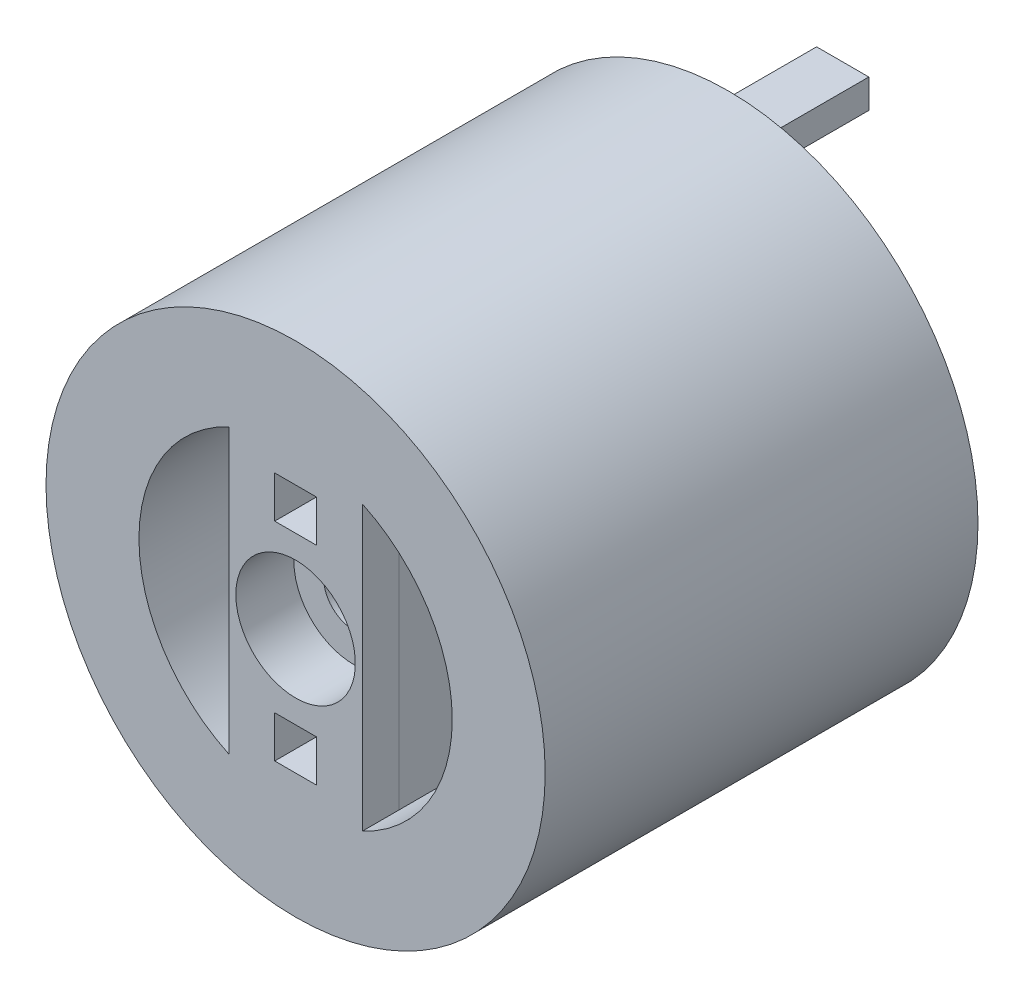
SolidWorks part; units mm, degrees
ref_plane "Front Plane" through (0, 0, 0) normal (0, 0, 1) x (1, 0, 0)
ref_plane "Top Plane" through (0, 0, 0) normal (0, 1, 0) x (1, 0, 0)
ref_plane "Right Plane" through (0, 0, 0) normal (1, 0, 0) x (0, 0, -1)
sketch "Sketch1" plane through (0, 0, 0) normal (0, 0, 1) x (1, 0, 0)
  line L0 (14.5003, 0) -> (13.5003, 0)
  line L1 (0, 16.2503) -> (0, 13.5003)
  line L3 (0, -13.5003) -> (0, -21.51)
  line L4 (13.5003, 0) -> (-13.5003, 0)
  line L8 (19.5347, 4.9654) -> (14.5348, 4.9999)
  line L9 (19.5347, 4.9654) -> (19.4657, -5.0344)
  line L10 (19.4657, -5.0344) -> (14.4659, -4.9999)
  line L11 (14.5348, 4.9999) -> (14.4659, -4.9999)
  line L24 (-2.25, 18.7503) -> (-2.25, 16.2503)
  line L25 (-2.25, 18.7503) -> (2.25, 18.7503)
  line L26 (2.25, 18.7503) -> (2.25, 16.2503)
  line L27 (-2.25, 16.2503) -> (2.25, 16.2503)
  circle A0 centre (0, 0) radius 13.5003
  circle A1 centre (0, 0) radius 21.51
  point P0 (0, 16.2503)
  point P1 (14.5003, 0)
  dimension "D3" = 4.5
  dimension "D5" = 4.9
  dimension "D1" = 1
  dimension "D2" = 2.75
  dimension "D4" = 2.5
  dimension "D6" = 5
  dimension "D7" = 10
extrude "Boss-Extrude1" add sketch "Sketch1" along normal blind 37.3 contours A1 L11 L8 L9 L10 L27 L24 L25 L26 A0 | L24 L27 L26 L25 | L8 L11 L10 L9 | L3 A1 L9 L10 L11 L0 A0 region at (-14.7797, 14.7797, 0) region at (0, 17.5003, 0) region at (17.0003, -0.0172, 0)
extrude "Boss-Extrude2" add sketch "Sketch1<4>" against normal blind 9.85 contours L25 L26 L27 L24
sketch "Sketch1<4>" plane through (0, 0, 0) normal (0, 0, 1) x (1, 0, 0) same geometry as "Sketch1"
sketch "Sketch3" plane through (0, 0, 0) normal (0, 1, 0) x (1, 0, 0)
  line L0 (0, -26.5014) -> (0, 0)
pattern_circular "CirPattern2" count 2 over 360 about axis through (0, 0, 26.5014) along (0, 0, -1) of "Boss-Extrude2" reverse direction yes
sketch "Sketch4" plane through (0, 0, 37.3) normal (0, 0, 1) x (1, 0, 0)
  line L1 (5.75, -19.1684) -> (-5.75, -19.1684)
  line L2 (5.75, -19.1684) -> (5.75, 19.1684)
  line L3 (5.75, 19.1684) -> (-5.75, 19.1684)
  line L4 (-5.75, -19.1684) -> (-5.75, 19.1684)
  line L5 (5.75, -19.1684) -> (-5.75, 19.1684) construction
  line L6 (5.75, 19.1684) -> (-5.75, -19.1684) construction
  line L7 (-5.75, 5.75) -> (5.75, 5.75)
  line L8 (-5.75, 5.75) -> (-5.75, -5.75)
  line L9 (-5.75, -5.75) -> (5.75, -5.75)
  line L10 (5.75, 5.75) -> (5.75, -5.75)
  line L11 (-5.75, 5.75) -> (5.75, -5.75) construction
  line L12 (-5.75, -5.75) -> (5.75, 5.75) construction
  point P0 (0, 0)
  point P5 (0, 0)
  dimension "D1" = 11.5
extrude "Boss-Extrude3" add sketch "Sketch4" against normal blind 3.175 contours L4 L3 L2 L1
sketch "Sketch8" plane through (0, 0, 34.125) normal (0, 0, 1) x (1, 0, 0)
  line L0 (0, -2.5875) -> (0, -16.4823)
  line L5 (5.7476, 16.4823) -> (-5.7476, 16.4823)
  line L6 (5.7476, 16.4823) -> (5.7476, -16.4823)
  line L11 (5.7476, -16.4823) -> (-5.7476, -16.4823)
  line L12 (-5.7476, 16.4823) -> (-5.7476, -16.4823)
  line L13 (5.7476, 16.4823) -> (-5.7476, -16.4823) construction
  line L14 (5.7476, -16.4823) -> (-5.7476, 16.4823) construction
  circle A1 centre (0, 0) radius 2.5875
  point P0 (0, 0)
  dimension "D2" = 11.4952
extrude "Boss-Extrude4" add sketch "Sketch8" against normal blind 5 contours L5 L12 L11 L6 | A1
extrude "Cut-Extrude1" cut sketch "Sketch1<3>" along normal blind 23 contours L8 L11 L10 L9 region at (17.0003, -0.0172, 0)
sketch "Sketch1<3>" plane through (0, 0, 0) normal (0, 0, 1) x (1, 0, 0) same geometry as "Sketch1"
pattern_circular "CirPattern1" count 2 every 53 about axis through (0, 0, 26.5014) along (0, 0, -1) of "Cut-Extrude1" reverse direction yes other way count 2
mirror "Mirror2" about plane through (0, 0, 0) normal (1, 0, 0) of "CirPattern1"
sketch "Sketch7" plane through (0, 0, 37.3) normal (0, 0, 1) x (1, 0, 0)
  circle A0 centre (0, 0) radius 5.15
extrude "Cut-Extrude2" cut sketch "Sketch7" against normal blind 5 and the other way through all
sketch "Sketch11" plane through (0, 0, 37.3) normal (0, 0, -1) x (-1, 0, 0)
  line L0 (0, 7.15) -> (0, 5.15)
  line L1 (-1.8, 10.75) -> (1.8, 10.75)
  line L2 (-1.8, 10.75) -> (-1.8, 7.15)
  line L3 (-1.8, 7.15) -> (1.8, 7.15)
  line L4 (1.8, 10.75) -> (1.8, 7.15)
  line L5 (-1.8, 10.75) -> (1.8, 7.15) construction
  line L6 (-1.8, 7.15) -> (1.8, 10.75) construction
  circle A0 centre (0, 0) radius 5.15 construction
  point P0 (0, 8.95)
  dimension "D1" = 3.6
  dimension "D2" = 2
extrude "Cut-Extrude21" cut sketch "Sketch11" along normal blind 29 contours L1 L4 L3 L2 region at (0, 8.95, 37.3)
mirror "Mirror1" about plane through (0, 0, 0) normal (0, 1, 0) of "Cut-Extrude21"
